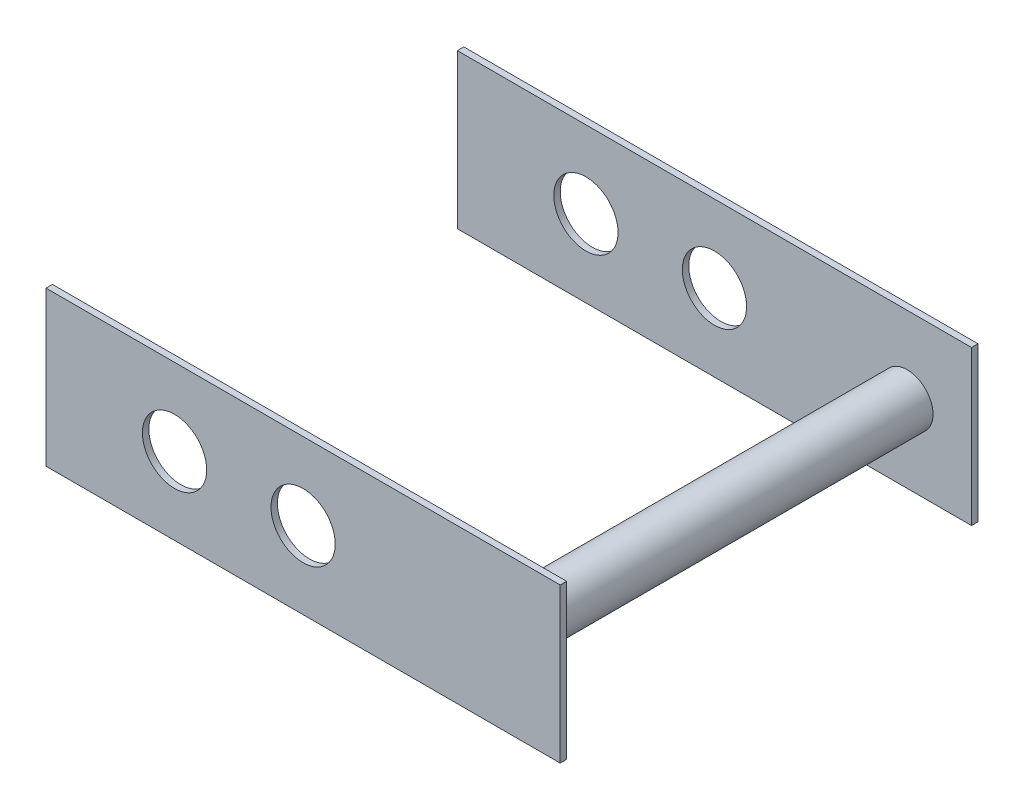
SolidWorks part; units mm, degrees
ref_plane "Front Plane" through (0, 0, 0) normal (0, 0, 1) x (1, 0, 0)
ref_plane "Top Plane" through (0, 0, 0) normal (0, 1, 0) x (1, 0, 0)
ref_plane "Right Plane" through (0, 0, 0) normal (1, 0, 0) x (0, 0, -1)
sketch "Sketch2" plane through (0, 0, 0) normal (0, 0, 1) x (1, 0, 0)
  line L4 (63.5, 38.1) -> (-63.5, 38.1)
  line L5 (63.5, -38.1) -> (63.5, 38.1)
  line L6 (-63.5, -38.1) -> (63.5, -38.1)
  line L7 (-63.5, 38.1) -> (-63.5, -38.1)
  line L8 (63.5, 38.1) -> (-63.5, 38.1)
  line L9 (63.5, -38.1) -> (63.5, 38.1)
  line L10 (-63.5, -38.1) -> (63.5, -38.1)
  line L11 (-63.5, 38.1) -> (-63.5, -38.1)
  circle A1 centre (25.4, 0) radius 12.7
  circle A2 centre (25.4, 0) radius 12.7
  dimension "D1" = 0
  dimension "D2" = 0
sketch "Sketch3" plane through (0, 0, 0) normal (0, 1, 0) x (1, 0, 0)
  line L4 (-63.5, 12.7) -> (-63.5, -25.4)
  line L5 (-63.5, -25.4) -> (63.5, -25.4)
  line L6 (63.5, -25.4) -> (63.5, 0)
  line L7 (-18.5941, 12.7) -> (-63.5, 12.7)
  line L8 (-63.5, 12.7) -> (-63.5, -25.4)
  line L9 (-63.5, -25.4) -> (63.5, -25.4)
  line L10 (63.5, -25.4) -> (63.5, 0)
  line L11 (-18.5941, 12.7) -> (-63.5, 12.7)
  arc A3 (63.5, 0) -> (25.4, 38.1) centre (25.4, 0) ccw
  arc A4 (25.4, 38.1) -> (-7.5956, 19.05) centre (25.4, 0) ccw
  arc A5 (-18.5941, 12.7) -> (-7.5956, 19.05) centre (-18.5941, 25.4) ccw
  arc A6 (63.5, 0) -> (25.4, 38.1) centre (25.4, 0) ccw
  arc A7 (25.4, 38.1) -> (-7.5956, 19.05) centre (25.4, 0) ccw
  arc A8 (-18.5941, 12.7) -> (-7.5956, 19.05) centre (-18.5941, 25.4) ccw
  dimension "D1" = 0
sketch "Sketch6" plane through (0, 0, 0) normal (0, 1, 0) x (1, 0, 0)
  line L0 (25.4, 88.9) -> (25.4, -76.2) construction
  line L1 (25.4, 88.9) -> (25.4, -76.2)
sketch "Sketch4" plane through (0, 0, 0) normal (0, 0, 1) x (1, 0, 0)
  circle A0 centre (25.4, 0) radius 12.7 construction
  circle A1 centre (25.4, 0) radius 12.7 construction
  circle A2 centre (25.4, 0) radius 10.16
  dimension "D1" = 2.54
extrude "Boss-Extrude1" add sketch "Sketch4" along normal up to vertex (76.2 mm away) and the other way up to vertex (88.9 mm away) up to point (25.4, 0, 76.2) other way up to point (25.4, 0, -88.9)
sketch "Sketch7" plane through (0, 0, -88.9) normal (0, 0, -1) x (-1, 0, 0)
  line L0 (152.4, 30.48) -> (152.4, -30.48) construction
  line L1 (-50.8, -30.48) -> (152.4, -30.48)
  line L2 (-50.8, -30.48) -> (-50.8, 30.48)
  line L3 (-50.8, 30.48) -> (152.4, 30.48)
  line L4 (152.4, -30.48) -> (152.4, 30.48)
  line L5 (152.4, -30.48) -> (63.5, -30.48) construction
  dimension "D1" = 25.4
extrude "Boss-Extrude2" add sketch "Sketch7" against normal blind 2.54
sketch "Sketch8" plane through (0, 0, 76.2) normal (0, 0, 1) x (1, 0, 0)
  line L4 (50.8, -30.48) -> (50.8, 30.48)
  line L5 (50.8, 30.48) -> (-152.4, 30.48)
  line L6 (-152.4, 30.48) -> (-152.4, -30.48)
  line L7 (-152.4, -30.48) -> (50.8, -30.48)
  line L8 (50.8, -30.48) -> (50.8, 30.48)
  line L9 (50.8, 30.48) -> (-152.4, 30.48)
  line L10 (-152.4, 30.48) -> (-152.4, -30.48)
  line L11 (-152.4, -30.48) -> (50.8, -30.48)
  dimension "D1" = 0
extrude "Boss-Extrude3" add sketch "Sketch8" against normal blind 2.54
sketch "Sketch9" plane through (0, 0, 76.2) normal (0, 0, 1) x (1, 0, 0)
  line L0 (-152.4, 0) -> (-50.8, 0) construction
  line L1 (-152.4, 30.48) -> (-152.4, -30.48) construction
  circle A0 centre (-50.8, 0) radius 12.7
  circle A1 centre (-101.6, 0) radius 12.7
  dimension "D1" = 25.4
  dimension "D2" = 101.6
extrude "Cut-Extrude1" cut sketch "Sketch9" against normal through all
